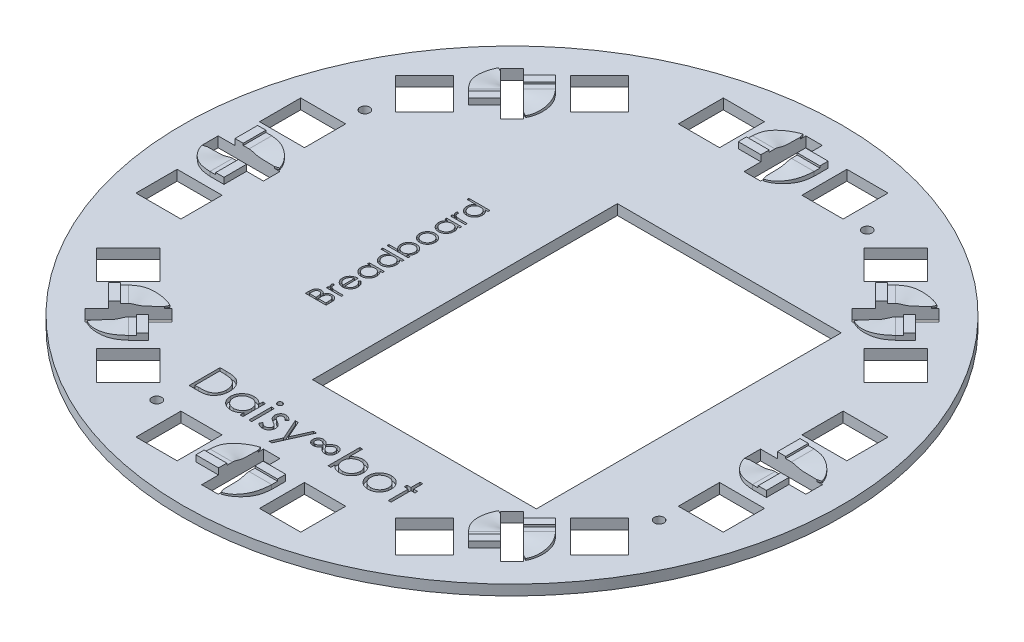
SolidWorks part; units mm, degrees
ref_plane "Front" through (0, 0, 0) normal (0, 0, 1) x (1, 0, 0)
ref_plane "Top" through (0, 0, 0) normal (0, 1, 0) x (1, 0, 0)
ref_plane "Right" through (0, 0, 0) normal (1, 0, 0) x (0, 0, -1)
sketch "Sketch1" plane through (0, 0, 0) normal (0, 1, 0) x (1, 0, 0)
  circle A0 centre (0, 0) radius 101.6
  dimension "D1" = 203.2
extrude "Base" add sketch "Sketch1" along normal blind 3.175 contours A0
sketch "Sketch2" plane through (0, 3.175, 0) normal (0, 1, 0) x (1, 0, 0)
  line L1 (-2.54, -93.1333) -> (2.54, -93.1333)
  line L2 (-2.54, -93.1333) -> (-2.54, -74.0833)
  line L3 (-2.54, -74.0833) -> (2.54, -74.0833)
  line L4 (2.54, -93.1333) -> (2.54, -74.0833)
  point P4 (0, -74.0833)
  dimension "D1" = 5.08
  dimension "D2" = 19.05
  dimension "D3" = 93.1333
extrude "Cut-Extrude1" cut sketch "Sketch2" against normal up to next and the other way through all contours L1 L4 L3 L2
sketch "Sketch4" plane through (0, 3.175, 0) normal (0, 1, 0) x (1, 0, 0)
  line L0 (0, -83.6083) -> (-2.9434, -74.5495) construction
  line L1 (-2.9434, -74.5495) -> (0, -83.6083) construction
  line L2 (0, -83.6083) -> (-5.5987, -75.9024) construction
  line L3 (0, -83.6083) -> (-7.7059, -78.0097) construction
  line L4 (0, -83.6083) -> (-9.0588, -80.6649) construction
  line L5 (0, -83.6083) -> (-9.525, -83.6083) construction
  line L9 (2.54, -74.0833) -> (-2.54, -74.0833) construction
  line L10 (2.54, -74.0833) -> (2.54, -93.1333) construction
  line L11 (-2.54, -74.0833) -> (-2.54, -93.1333) construction
  line L12 (2.54, -93.1333) -> (-2.54, -93.1333) construction
  circle A0 centre (0, -83.6083) radius 9.525 construction
  point P16 (0, -74.0833)
  point P19 (2.54, -83.6083)
  dimension "D1" = 18
  dimension "D2" = 18
  dimension "D3" = 18
  dimension "D4" = 18
  dimension "D5" = 18
ref_plane "Plane1" through (-24.5719, 0, 7.9839) normal (0.9511, 0, -0.309) x (-0.309, 0, -0.9511)
ref_plane "Plane2" through (-39.7581, 0, 28.886) normal (0.809, 0, -0.5878) x (-0.5878, 0, -0.809)
ref_plane "Plane3" through (-39.7581, 0, 54.7224) normal (0.5878, 0, -0.809) x (-0.809, 0, -0.5878)
ref_plane "Plane4" through (-24.5719, 0, 75.6244) normal (0.309, 0, -0.9511) x (-0.9511, 0, -0.309)
ref_plane "Plane5" through (0, 0, 83.6083) normal (0, 0, -1) x (-1, 0, 0)
sketch "Sketch5" plane through (-24.5719, 0, 7.9839) normal (0.9511, 0, -0.309) x (-0.309, 0, -0.9511)
  line L0 (-69.6725, 3.175) -> (-87.7902, 3.175) construction
  line L1 (-71.2966, 3.175) -> (-69.9913, 3.175)
  line L2 (-71.2966, 3.175) -> (-71.2966, 3.683)
  line L3 (-71.2966, 3.683) -> (-69.9913, 3.683)
  line L4 (-69.9913, 3.175) -> (-69.9913, 3.683)
  dimension "D2" = 0.508
sketch "Sketch6" plane through (-39.7581, 0, 28.886) normal (0.809, 0, -0.5878) x (-0.5878, 0, -0.809)
  line L0 (-58.4417, 3.175) -> (-73.8535, 3.175) construction
  line L1 (-63.3193, 3.175) -> (-58.1156, 3.175)
  line L2 (-63.3193, 3.175) -> (-63.3193, 3.775)
  line L3 (-63.3193, 3.775) -> (-58.1156, 3.775)
  line L4 (-58.1156, 3.175) -> (-58.1156, 3.775)
  dimension "D2" = 0.6
sketch "Sketch7" plane through (-39.7581, 0, 54.7224) normal (0.5878, 0, -0.809) x (-0.809, 0, -0.5878)
  line L0 (-41.4902, 3.175) -> (-52.6875, 3.175) construction
  line L1 (-46.0041, 3.175) -> (-39.6187, 3.175)
  line L2 (-46.0041, 3.175) -> (-46.0041, 4.075)
  line L3 (-46.0041, 4.075) -> (-39.6187, 4.075)
  line L4 (-39.6187, 3.175) -> (-39.6187, 4.075)
  dimension "D2" = 0.9
sketch "Sketch10" plane through (-24.5719, 0, 75.6244) normal (0.309, 0, -0.9511) x (-0.9511, 0, -0.309)
  line L0 (-25.8364, 3.175) -> (-16.7776, 3.175) construction
  line L1 (-23.1657, 3.175) -> (-16.3114, 3.175)
  line L2 (-23.1657, 3.175) -> (-23.1657, 4.375)
  line L3 (-23.1657, 4.375) -> (-16.3114, 4.375)
  line L4 (-16.3114, 3.175) -> (-16.3114, 4.375)
  dimension "D3" = 1.2
sketch "Sketch11" plane through (0, 0, 83.6083) normal (0, 0, -1) x (-1, 0, 0)
  line L0 (0, 3.175) -> (9.525, 3.175) construction
  line L1 (2.54, 3.175) -> (9.525, 3.175)
  line L2 (2.54, 3.175) -> (2.54, 4.475)
  line L3 (2.54, 4.475) -> (9.525, 4.475)
  line L4 (9.525, 3.175) -> (9.525, 4.475)
  dimension "D3" = 1.3
loft "Loft1" add profiles "Sketch5", "Sketch6", "Sketch7", "Sketch10", "Sketch11" connector at (-2.54, 3.683, 75.791) connector at (-2.54, 3.775, 80.1123) connector at (-2.54, 4.075, 81.7629) connector at (-2.54, 4.375, 82.783) connector at (-2.54, 4.475, 83.6083)
sketch "Sketch13" plane through (-104.9799, 0, 83.6083) normal (0, 0, -1) x (-1, 0, 0)
  line L6 (-95.4549, 3.175) -> (-102.4399, 3.175)
  line L7 (-95.4549, 3.175) -> (-95.4549, 4.475)
  line L8 (-95.4549, 4.475) -> (-102.4399, 4.475)
  line L9 (-102.4399, 3.175) -> (-102.4399, 4.475)
extrude "Boss-Extrude4" add sketch "Sketch13" against normal blind 1.7907
sketch "Sketch25" plane through (0, 0, 85.399) normal (0, 0, 1) x (1, 0, 0)
  line L0 (-9.525, 4.475) -> (-2.54, 4.475) construction
  line L1 (-9.525, 3.175) -> (-2.54, 3.175)
  line L2 (-9.525, 3.175) -> (-9.525, 5.075)
  line L3 (-9.525, 5.075) -> (-2.54, 5.075)
  line L4 (-2.54, 3.175) -> (-2.54, 5.075)
  dimension "D1" = 0.6
extrude "Boss-Extrude5" add sketch "Sketch25" along normal blind 2.54
sketch "Sketch14" plane through (-2.54, 0, 0) normal (1, 0, 0) x (0, 0, -1)
  line L0 (-83.6083, 3.175) -> (-83.6083, 0) construction
  line L1 (-74.0833, 0) -> (-93.1333, 0) construction
ref_plane "Plane6" through (0, 0, 0) normal (1, 0, 0) x (0, 0, -1)
sketch "Sketch15" plane through (0, 0, 0) normal (1, 0, 0) x (0, 0, -1)
  line L0 (-83.6083, 0) -> (-83.6083, 3.175) construction
pattern_circular "CirPattern1" count 2 over 360 about axis through (0, 0, 83.6083) along (0, 1, 0) of "Loft1", "Boss-Extrude5", "Boss-Extrude4" reverse direction yes
ref_axis "Axis1" through (0, 50, 0) along (0, -1, 0)
pattern_circular "CirPattern5" count 8 over 360 about axis through (0, 50, 0) along (0, -1, 0) of "CirPattern1", "Cut-Extrude1"
sketch "Sketch18" plane through (0, 3.175, 0) normal (0, 1, 0) x (1, 0, 0)
  line L4 (0, -101.6) -> (0, 101.6) construction
  line L5 (0, -1.7463) -> (0, 1.7463) construction
  line L6 (-101.6, 0) -> (101.6, 0) construction
  line L9 (-13.5, -48) -> (55.5, -48)
  line L10 (-13.5, -48) -> (-13.5, 46)
  line L11 (-13.5, 46) -> (55.5, 46)
  line L12 (55.5, -48) -> (55.5, 46)
  circle A8 centre (0, 0) radius 101.6 construction
  point P28 (48.26, 44.45)
  dimension "D1" = 13.5
  dimension "D2" = 46
  dimension "D3" = 94
  dimension "D4" = 69
sketch "Sketch19" plane through (0, 3.175, 0) normal (0, 1, 0) x (1, 0, 0)
  line L0 (-32.0765, -77.4396) -> (0, 0) construction
  line L1 (0, -101.6) -> (0, 101.6) construction
  circle A1 centre (-32.0765, -77.4396) radius 1.5
  circle A4 centre (0, 0) radius 101.6 construction
  dimension "D4" = 3
  dimension "D6" = 83.82
  dimension "D5" = 22.5
extrude "Cut-Extrude2" cut sketch "Sketch19" against normal through all
pattern_circular "CirPattern7" count 4 over 360 about axis through (0, 50, 0) along (0, -1, 0) of "Cut-Extrude2"
sketch "Sketch23" plane through (0, 3.175, 0) normal (0, 1, 0) x (1, 0, 0)
  line L9 (-2.54, -87.939) -> (-2.54, -93.1333) construction
  line L10 (-25.4, -76.6805) -> (-12.7, -76.6805)
  line L11 (-25.4, -76.6805) -> (-25.4, -90.5362)
  line L16 (-25.4, -90.5362) -> (-12.7, -90.5362)
  line L17 (-12.7, -76.6805) -> (-12.7, -90.5362)
  line L19 (2.54, -74.0833) -> (2.54, -79.2776) construction
  line L20 (0, -50) -> (0, 50) construction
  line L21 (12.7, -76.6805) -> (12.7, -90.5362)
  line L22 (25.4, -90.5362) -> (12.7, -90.5362)
  line L23 (25.4, -76.6805) -> (25.4, -90.5362)
  line L24 (25.4, -76.6805) -> (12.7, -76.6805)
  point P8 (-2.54, -90.5362)
  point P9 (2.54, -76.6805)
  dimension "D1" = 12.7
  dimension "D2" = 10.16
extrude "Cut-Extrude6" cut sketch "Sketch23" against normal through all
pattern_circular "CirPattern8" count 8 over 360 about axis through (0, 50, 0) along (0, -1, 0) of "Cut-Extrude6"
sketch "Sketch17" plane through (0, 3.175, 0) normal (0, 1, 0) x (1, 0, 0)
  line L0 (33.02, -68.58) -> (-33.02, -68.58) construction
  line L1 (2.54, -74.0833) -> (-2.54, -74.0833) construction
  point P3 (0, -68.58)
  point P7 (0, -74.0833)
  dimension "D2" = 68.58
  dimension "D1" = 66.04
sketch "Sketch16" plane through (0, 3.175, 0) normal (0, 1, 0) x (1, 0, 0)
  line L0 (33.02, -68.58) -> (-33.02, -68.58) construction
  text T0 "Daisy∞bot\r\n" font "Century Gothic" height in points 36
extrude "Cut-Extrude4" cut sketch "Sketch16" against normal blind 1.27
sketch "Sketch22" plane through (0, 3.175, 0) normal (0, 1, 0) x (1, 0, 0)
  line L0 (-31.3017, 25.1735) -> (-31.3017, -33.6024) construction
  text T0 "Breadboard"
extrude "Cut-Extrude5" cut sketch "Sketch22" against normal blind 1.27
extrude "Cut-Extrude7" cut sketch "Sketch18" against normal through all
